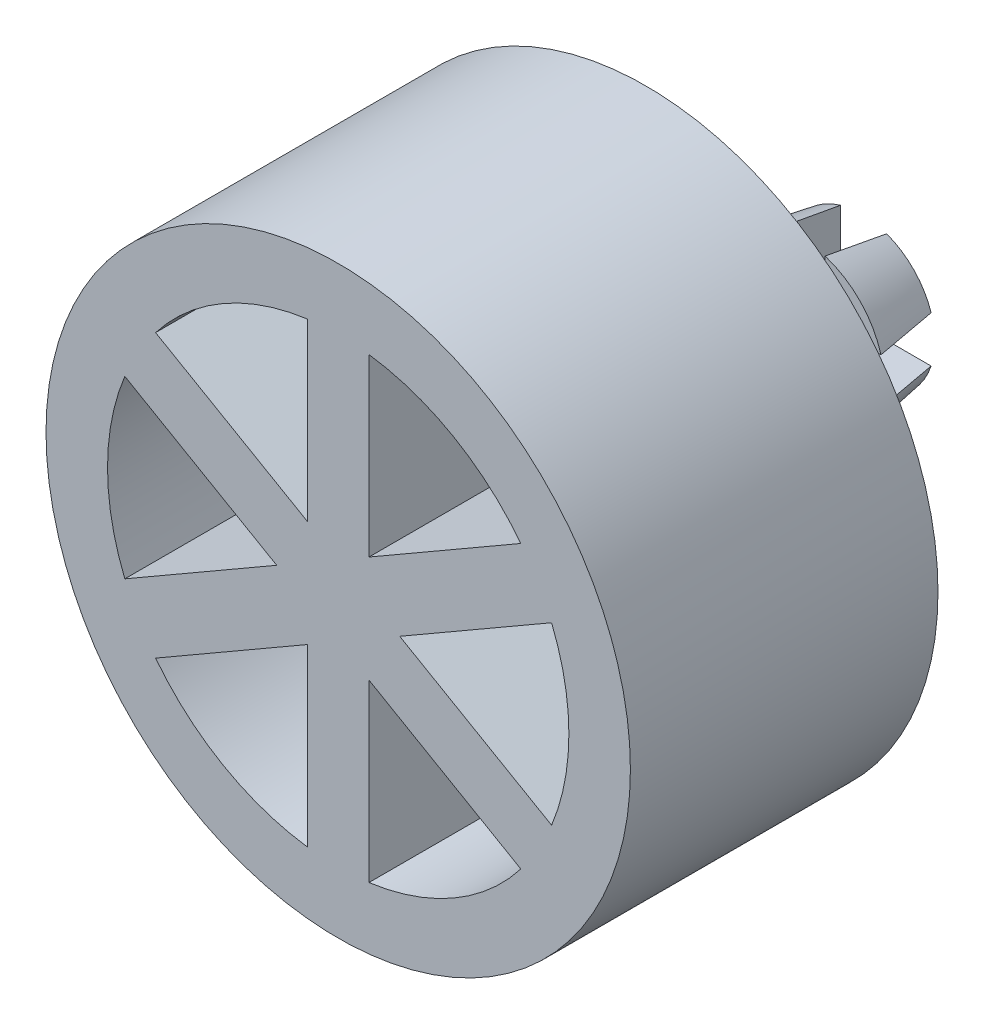
SolidWorks part; units mm, degrees
ref_plane "Płaszczyzna przednia" through (0, 0, 0) normal (0, 0, 1) x (1, 0, 0)
ref_plane "Płaszczyzna górna" through (0, 0, 0) normal (0, 1, 0) x (1, 0, 0)
ref_plane "Płaszczyzna prawa" through (0, 0, 0) normal (1, 0, 0) x (0, 0, -1)
sketch "Szkic1" plane through (0, 0, 0) normal (0, 0, 1) x (1, 0, 0)
  line L0 (-5.9372, -4.5825) -> (-1, -1.7321)
  line L2 (1, -7.433) -> (1, -1.7321)
  line L4 (-1, -7.433) -> (-1, -1.7321)
  line L5 (0.9912, -7.4342) -> (0.2643, -1.9825) construction
  line L6 (0.9912, 7.4342) -> (0.2643, 1.9825) construction
  line L8 (-6.9372, -2.8505) -> (-2, 0)
  line L10 (-6.9372, 2.8505) -> (-2, 0)
  line L12 (-5.9372, 4.5825) -> (-1, 1.7321)
  line L14 (2, 0) -> (6.9372, -2.8505)
  line L15 (-0.2643, -1.9825) -> (-0.9912, -7.4342) construction
  line L19 (-0.2643, 1.9825) -> (-0.9912, 7.4342) construction
  line L21 (1, 1.7321) -> (5.9372, 4.5825)
  line L22 (1, 1.7321) -> (1, 7.433)
  line L23 (2, 0) -> (6.9372, 2.8505)
  line L24 (1, -1.7321) -> (5.9372, -4.5825)
  line L28 (-1, 1.7321) -> (-1, 7.433)
  circle A0 centre (0, 0) radius 2
  circle A1 centre (0, 0) radius 7.5
  circle A2 centre (0, 0) radius 9.5
  point P5 (0, 0)
  point P21 (0, 0)
  dimension "D1" = 4
  dimension "D2" = 15
  dimension "D3" = 2
  dimension "D5" = 3
extrude "Dodanie-wyciągnięcie1" add sketch "Szkic1" along normal blind 10 contours L22 A1 L28 A0 | A0 | L23 A1 L21 A0 | L24 A1 L14 A0 | L4 A1 L2 A0 | L8 A1 L0 A0 | L12 A1 L10 A0 | A2 A1 L21 L23 L14 L24 L2 L4 L0 L8 L10 L12 L28 L22 region at (-4.0659, -2.3475, 0) region at (0, -4.6949, 0) region at (0, 0, 0) region at (-4.0659, 2.3475, 0) region at (4.0659, -2.3475, 0) region at (0, 4.6949, 0) region at (4.0659, 2.3475, 0) region at (-9.2313, 0, 0)
sketch "Szkic2" plane through (0, 0, 0) normal (0, 0, -1) x (-1, 0, 0)
  circle A0 centre (0, 0) radius 2
  dimension "D1" = 4
extrude "Dodanie-wyciągnięcie2" add sketch "Szkic2" along normal blind 5
sketch "Szkic3" plane through (0, 0, -5) normal (0, 0, -1) x (-1, 0, 0)
  circle A0 centre (0, 0) radius 2.75
  dimension "D1" = 5.5
extrude "Dodanie-wyciągnięcie3" add sketch "Szkic3" along normal blind 2 draft 10
sketch "Szkic4" plane through (0, 0, -7) normal (0, 0, -1) x (-1, 0, 0)
  line L1 (0.6699, -8.4237) -> (-0.8301, -8.4237)
  line L2 (0.6699, -8.4237) -> (0.6699, 8.4237)
  line L3 (0.6699, 8.4237) -> (-0.8301, 8.4237)
  line L4 (-0.8301, -8.4237) -> (-0.8301, 8.4237)
  line L5 (0.6699, -8.4237) -> (-0.8301, 8.4237) construction
  line L6 (0.6699, 8.4237) -> (-0.8301, -8.4237) construction
  point P0 (-0.0801, 0)
  point P1 (0, 0)
  dimension "D1" = 0.75
extrude "Wytnij-wyciągnięcie1" cut sketch "Szkic4" against normal up to surface (7 mm away) contours L4 L3 L2 L1 up to face at (0, 0, 0)
sketch "Szkic5" plane through (0, 0, 0) normal (0, 0, -1) x (-1, 0, 0)
  line L1 (11.1845, -0.7508) -> (-11.1614, -0.7508)
  line L2 (11.1845, -0.7508) -> (11.1845, 0.7492)
  line L3 (11.1845, 0.7492) -> (-11.1614, 0.7492)
  line L4 (-11.1614, -0.7508) -> (-11.1614, 0.7492)
  line L5 (11.1845, -0.7508) -> (-11.1614, 0.7492) construction
  line L6 (11.1845, 0.7492) -> (-11.1614, -0.7508) construction
  point P0 (0, 0)
  dimension "D1" = 1.5
extrude "Wytnij-wyciągnięcie2" cut sketch "Szkic5" along normal up to surface (7 mm away) up to face at (-1.5336, 0, -7)
